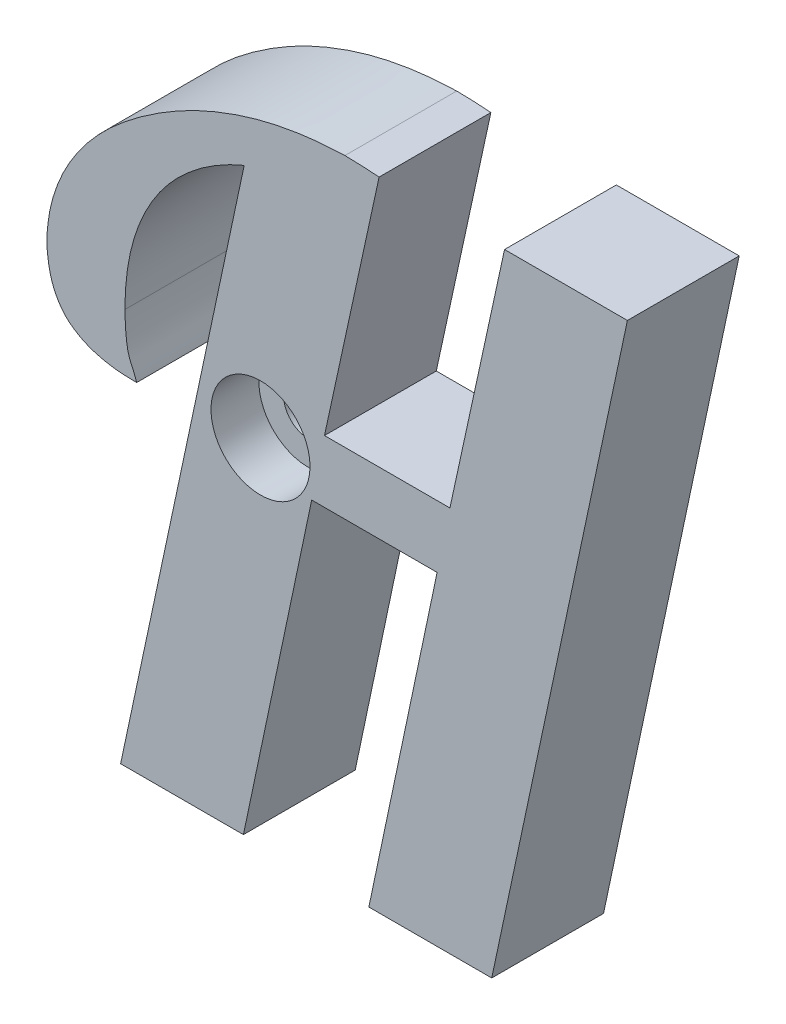
SolidWorks part; units mm, degrees
ref_plane "Front Plane" through (0, 0, 0) normal (0, 0, 1) x (1, 0, 0)
ref_plane "Top Plane" through (0, 0, 0) normal (0, 1, 0) x (1, 0, 0)
ref_plane "Right Plane" through (0, 0, 0) normal (1, 0, 0) x (0, 0, -1)
sketch "Sketch1" plane through (0, 0, 0) normal (0, 0, 1) x (1, 0, 0)
  text T0 "H" font "Lobster 1.4" height 40
extrude "Extrude1" add sketch "Sketch1" along normal blind 7
sketch "Sketch2" plane through (0, 0, 7) normal (0, 0, 1) x (1, 0, 0)
  line L2 (27.8587, 36.83) -> (16.2323, 37.2204) construction
  circle A0 centre (20.433, 18.9737) radius 3.1
  dimension "D1" = 6.2
extrude "Extrude2" cut sketch "Sketch2" against normal blind 3
sketch "Sketch3" plane through (0, 0, 4) normal (0, 0, 1) x (1, 0, 0)
  circle A0 centre (20.433, 18.9737) radius 1.55
  dimension "D1" = 3.1
extrude "Extrude3" cut sketch "Sketch3" against normal blind 13
